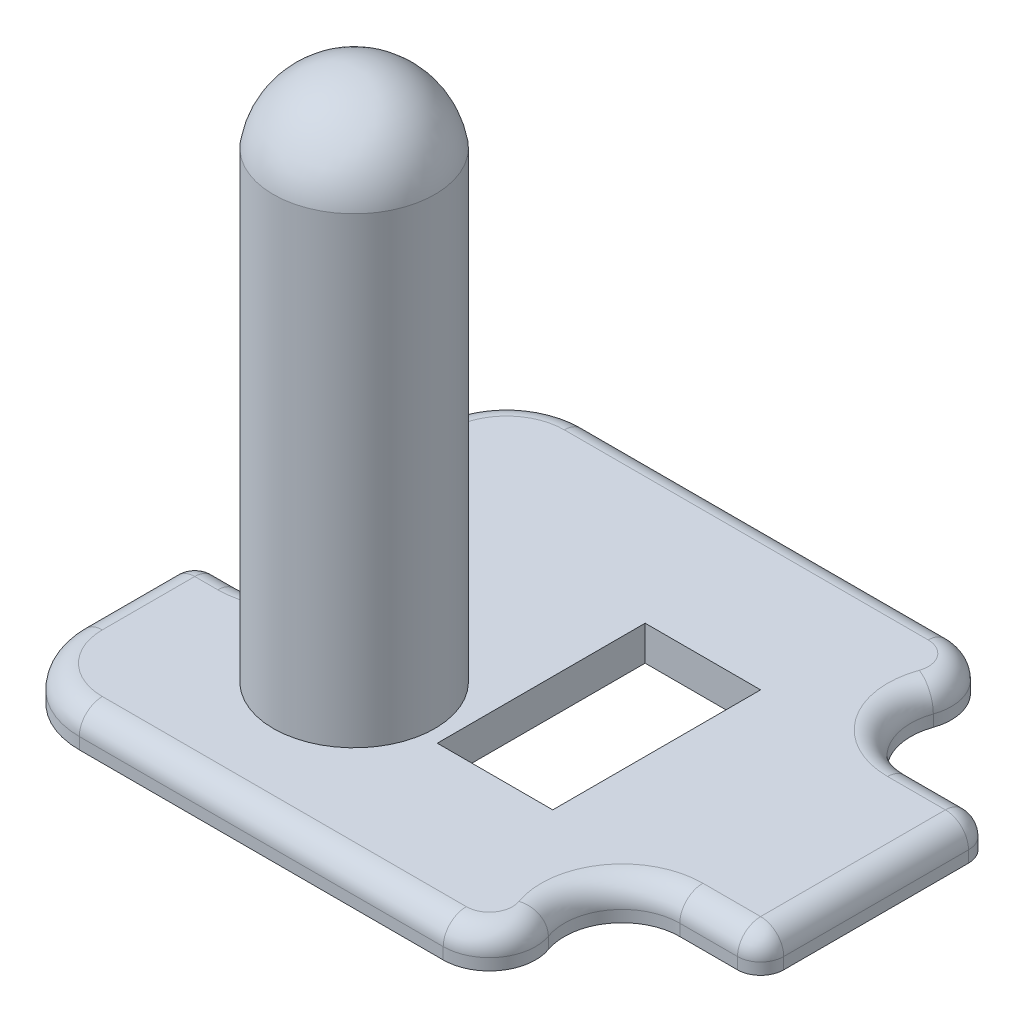
SolidWorks part; units mm, degrees
ref_plane "Alzado" through (0, 0, 0) normal (0, 0, 1) x (1, 0, 0)
ref_plane "Planta" through (0, 0, 0) normal (0, 1, 0) x (1, 0, 0)
ref_plane "Vista lateral" through (0, 0, 0) normal (1, 0, 0) x (0, 0, -1)
sketch "Croquis1" plane through (0, 155.4998, 0) normal (0, 1, 0) x (1, 0, 0)
  line L9 (1.8817, 20.085) -> (1.8817, 36.085)
  line L10 (-0.1183, 38.085) -> (-5.1183, 38.085)
  line L11 (-13.6035, 50.085) -> (-45.1183, 50.085)
  line L12 (-52.1183, 43.085) -> (-52.1183, 35.085)
  line L13 (-50.1183, 33.085) -> (-48.1183, 33.085)
  line L14 (-48.1183, 23.085) -> (-50.1183, 23.085)
  line L15 (-52.1183, 21.085) -> (-52.1183, 13.085)
  line L16 (-45.1183, 6.085) -> (-13.6035, 6.085)
  line L17 (-5.1183, 18.085) -> (-0.1183, 18.085)
  line L18 (1.8817, 20.085) -> (1.8817, 36.085)
  line L19 (-0.1183, 38.085) -> (-5.1183, 38.085)
  line L20 (-13.6035, 50.085) -> (-45.1183, 50.085)
  line L21 (-52.1183, 43.085) -> (-52.1183, 35.085)
  line L22 (-50.1183, 33.085) -> (-48.1183, 33.085)
  line L23 (-48.1183, 23.085) -> (-50.1183, 23.085)
  line L24 (-52.1183, 21.085) -> (-52.1183, 13.085)
  line L25 (-45.1183, 6.085) -> (-13.6035, 6.085)
  line L26 (-5.1183, 18.085) -> (-0.1183, 18.085)
  arc A11 (1.8817, 36.085) -> (-0.1183, 38.085) centre (-0.1183, 36.085) ccw
  arc A12 (-9.8323, 44.7516) -> (-5.1183, 38.085) centre (-5.1183, 43.085) ccw
  arc A13 (-9.8323, 44.7516) -> (-13.6035, 50.085) centre (-13.6035, 46.085) ccw
  arc A14 (-45.1183, 50.085) -> (-52.1183, 43.085) centre (-45.1183, 43.085) ccw
  arc A15 (-52.1183, 35.085) -> (-50.1183, 33.085) centre (-50.1183, 35.085) ccw
  arc A16 (-48.1183, 23.085) -> (-48.1183, 33.085) centre (-48.1183, 28.085) ccw
  arc A17 (-50.1183, 23.085) -> (-52.1183, 21.085) centre (-50.1183, 21.085) ccw
  arc A18 (-52.1183, 13.085) -> (-45.1183, 6.085) centre (-45.1183, 13.085) ccw
  arc A19 (-13.6035, 6.085) -> (-9.8323, 11.4183) centre (-13.6035, 10.085) ccw
  arc A20 (-5.1183, 18.085) -> (-9.8323, 11.4183) centre (-5.1183, 13.085) ccw
  arc A21 (-0.1183, 18.085) -> (1.8817, 20.085) centre (-0.1183, 20.085) ccw
  arc A22 (1.8817, 36.085) -> (-0.1183, 38.085) centre (-0.1183, 36.085) ccw
  arc A23 (-9.8323, 44.7516) -> (-5.1183, 38.085) centre (-5.1183, 43.085) ccw
  arc A24 (-9.8323, 44.7516) -> (-13.6035, 50.085) centre (-13.6035, 46.085) ccw
  arc A25 (-45.1183, 50.085) -> (-52.1183, 43.085) centre (-45.1183, 43.085) ccw
  arc A26 (-52.1183, 35.085) -> (-50.1183, 33.085) centre (-50.1183, 35.085) ccw
  arc A27 (-48.1183, 23.085) -> (-48.1183, 33.085) centre (-48.1183, 28.085) ccw
  arc A28 (-50.1183, 23.085) -> (-52.1183, 21.085) centre (-50.1183, 21.085) ccw
  arc A29 (-52.1183, 13.085) -> (-45.1183, 6.085) centre (-45.1183, 13.085) ccw
  arc A30 (-13.6035, 6.085) -> (-9.8323, 11.4183) centre (-13.6035, 10.085) ccw
  arc A31 (-5.1183, 18.085) -> (-9.8323, 11.4183) centre (-5.1183, 13.085) ccw
  arc A32 (-0.1183, 18.085) -> (1.8817, 20.085) centre (-0.1183, 20.085) ccw
  dimension "D1" = 0
extrude "Saliente-Extruir1" add sketch "Croquis1" along normal blind 3
sketch "Croquis2" plane through (0, 158.4998, 0) normal (0, 1, 0) x (1, 0, 0)
  line L0 (1.8817, 20.085) -> (1.8817, 36.085) construction
  line L1 (-27.1183, 19.085) -> (-17.1183, 19.085)
  line L2 (-27.1183, 19.085) -> (-27.1183, 37.085)
  line L3 (-27.1183, 37.085) -> (-17.1183, 37.085)
  line L4 (-17.1183, 19.085) -> (-17.1183, 37.085)
  line L5 (-27.1183, 19.085) -> (-17.1183, 37.085) construction
  line L6 (-27.1183, 37.085) -> (-17.1183, 19.085) construction
  line L7 (-13.6035, 50.085) -> (-45.1183, 50.085) construction
  point P0 (-22.1183, 28.085)
  point P5 (-22.4304, 28.1726)
  dimension "D1" = 24
  dimension "D2" = 22
  dimension "D3" = 18
  dimension "D4" = 10
extrude "Cortar-Extruir1" cut sketch "Croquis2" against normal up to next
sketch "Croquis3" plane through (0, 158.4998, 0) normal (0, 1, 0) x (1, 0, 0)
  circle A0 centre (-35.3183, 20.085) radius 4 construction
  circle A1 centre (-35.3183, 20.085) radius 4 construction
  circle A2 centre (-35.3183, 20.085) radius 5
  circle A3 centre (-35.3183, 20.085) radius 7 construction
  dimension "D1" = 1
  dimension "D2" = 2
extrude "Cortar-Extruir2" cut sketch "Croquis3" against normal up to next
sketch "Croquis4" plane through (0, 158.4998, 0) normal (0, 1, 0) x (1, 0, 0)
  circle A0 centre (-35.3183, 20.085) radius 5 construction
  circle A1 centre (-35.3183, 20.085) radius 5
  circle A2 centre (-35.3183, 20.085) radius 7
  dimension "D1" = 2
extrude "Saliente-Extruir2" add sketch "Croquis4" along normal blind 40
sketch "Croquis5" plane through (0, 198.4998, 0) normal (0, 1, 0) x (1, 0, 0)
  circle A0 centre (-35.3183, 20.085) radius 7 construction
  circle A1 centre (-35.3183, 20.085) radius 7
extrude "Saliente-Extruir3" add sketch "Croquis5" along normal blind 0.05
dome "Cúpula1" faces to dome 1 distance 6 reverse direction no elliptical dome no face at (-35.3183, 198.5498, -13.085) parameters "D1"=6
fillet "Redondeo1" radius 2 20 edges at (-50.068, 158.4998, -8.1352) (-52.1183, 158.4998, -17.085) (-51.5325, 158.4998, -22.4992) (-49.1183, 158.4998, -23.085) (-43.1183, 158.4998, -28.085) (-49.1183, 158.4998, -33.085) (-51.5325, 158.4998, -33.6708) (-52.1183, 158.4998, -39.085) (-50.068, 158.4998, -48.0347) (-29.3609, 158.4998, -50.085) (-10.3375, 158.4998, -48.3944) (-9.2007, 158.4998, -40.1982) (-2.6183, 158.4998, -38.085) (1.296, 158.4998, -37.4992) (1.8817, 158.4998, -28.085) (1.296, 158.4998, -18.6708) (-2.6183, 158.4998, -18.085) (-9.2007, 158.4998, -15.9717) (-10.3375, 158.4998, -7.7756) (-29.3609, 158.4998, -6.085)
